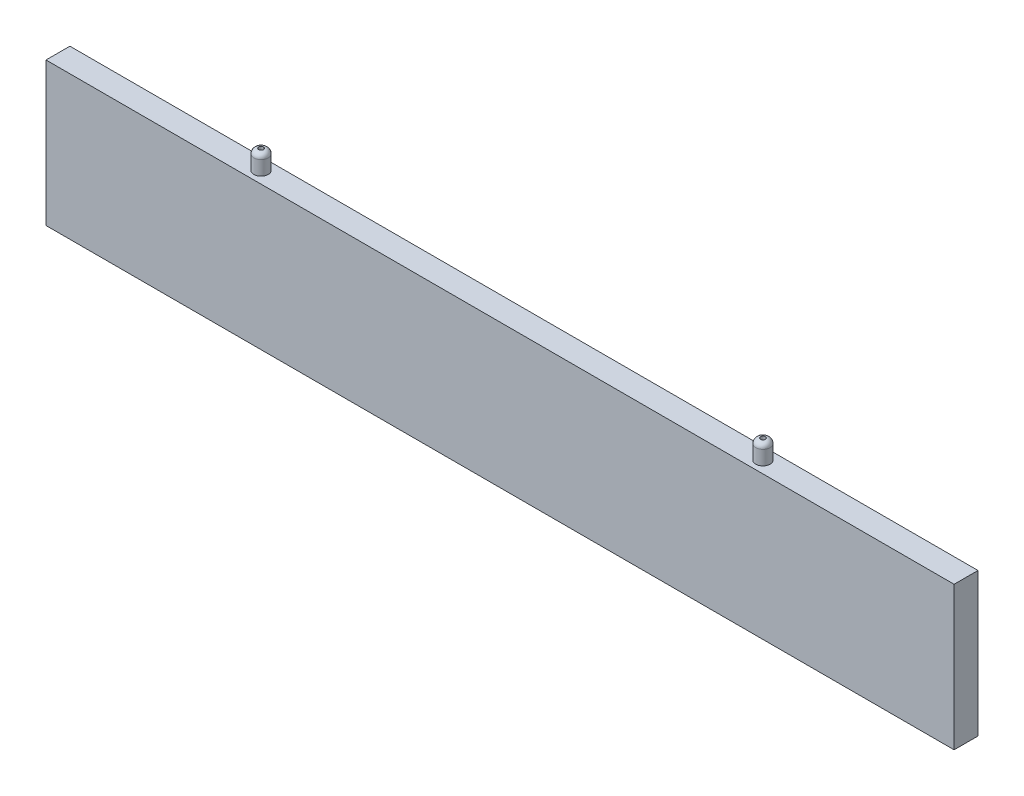
SolidWorks part; units mm, degrees
ref_plane "Plan de face" through (0, 0, 0) normal (0, 0, 1) x (1, 0, 0)
ref_plane "Plan de dessus" through (0, 0, 0) normal (0, 1, 0) x (1, 0, 0)
ref_plane "Plan de droite" through (0, 0, 0) normal (1, 0, 0) x (0, 0, -1)
sketch "Esquisse1" plane through (0, 0, 0) normal (0, 0, 1) x (1, 0, 0)
  line L1 (-95, 15) -> (95, 15)
  line L2 (-95, 15) -> (-95, -15)
  line L3 (-95, -15) -> (95, -15)
  line L4 (95, 15) -> (95, -15)
  line L5 (-95, 15) -> (95, -15) construction
  line L6 (-95, -15) -> (95, 15) construction
  point P0 (0, 0)
  dimension "D1" = 190
  dimension "D2" = 30
extrude "Boss.-Extru.1" add sketch "Esquisse1" along normal blind 5
sketch "Esquisse2" plane through (0, 15, 0) normal (0, 1, 0) x (1, 0, 0)
  line L0 (95, 0) -> (-95, 0) construction
  line L1 (0, 0) -> (0, -11.0338) construction
  circle A0 centre (-52.5, -2.5) radius 1.5
  circle A1 centre (-52.5, -2.5) radius 0.5
  circle A2 centre (52.5, -2.5) radius 0.5
  circle A3 centre (52.5, -2.5) radius 1.5
  dimension "D3" = 3
  dimension "D4" = 1
  dimension "D1" = 2.5
  dimension "D2" = 52.5
extrude "Boss.-Extru.2" add sketch "Esquisse2" along normal blind 4
fillet "Congé1" radius 1 2 edges at (52.5, 19, 1) (-52.5, 19, 4)
